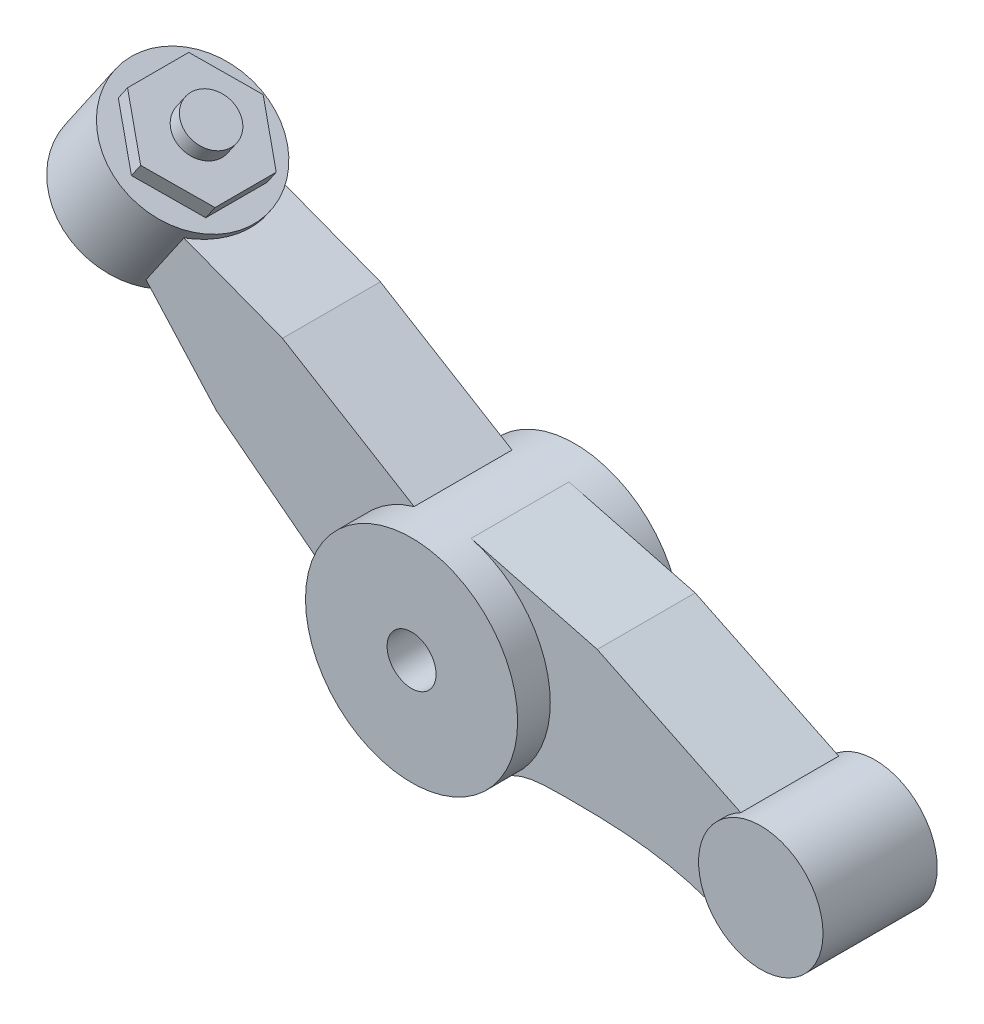
SolidWorks part; units mm, degrees
ref_plane "Front Plane" through (0, 0, 0) normal (0, 0, 1) x (1, 0, 0)
ref_plane "Top Plane" through (0, 0, 0) normal (0, 1, 0) x (1, 0, 0)
ref_plane "Right Plane" through (0, 0, 0) normal (1, 0, 0) x (0, 0, -1)
sketch "Sketch1" plane through (0, 0, 0) normal (0, 0, 1) x (1, 0, 0)
  line L0 (0, 0) -> (3.9859, 0) construction
  line L1 (0, 1.5974) -> (0, -1.3448) construction
  line L2 (0, 0) -> (-3.6604, 2.5129) construction
  line L3 (3.635, 0) -> (1.8753, 0.8528)
  line L4 (1.8753, 0.8528) -> (0.3293, 1.2576)
  line L5 (-3.468, 2.7932) -> (-3.8529, 2.2326)
  line L6 (-3.468, 2.7932) -> (-1.9822, 2.2255)
  line L7 (-1.9822, 2.2255) -> (-0.3688, 1.2466)
  line L8 (-2.7892, 1.0501) -> (-1.2958, -0.1038)
  line L9 (-3.8529, 2.2326) -> (-2.7892, 1.0501)
  circle A0 centre (0, 0) radius 0.3
  circle A1 centre (0, 0) radius 1.3
  circle A2 centre (3.98, -0.68) radius 0.7625
  spline S0 degree 3 poles (3.4329, -1.2112) (2.7827, -0.9275) (1.9247, -0.8957) (0.9499, -0.9165) (0.7651, -1.051) knots 0 0 0 0 0.749641 1 1 1 1
  dimension "D1" = 0.6
  dimension "D2" = 2.6
  dimension "D3" = 1.525
  dimension "D4" = 0.68
  dimension "D5" = 3.98
  dimension "D6" = 4.44
  dimension "D7" = 0.68
  dimension "D8" = 0.819
  dimension "D9" = 34.47
extrude "Boss-Extrude1" add sketch "Sketch1" along normal mid plane 2 contours A1 A0 region at (1, 0.7718, 0)
extrude "Boss-Extrude2" add sketch "Sketch1<3>" along normal mid plane 1.4 separate body contours A2 region at (3.98, -0.68, 0)
sketch "Sketch1<3>" plane through (0, 0, 0) normal (0, 0, 1) x (1, 0, 0) same geometry as "Sketch1"
extrude "Boss-Extrude3" add sketch "Sketch1<4>" along normal mid plane 1.2 contours S0 A2 L3 L4 A1 region at (2.1488, -0.1092, 0)
sketch "Sketch1<4>" plane through (0, 0, 0) normal (0, 0, 1) x (1, 0, 0) same geometry as "Sketch1"
extrude "Boss-Extrude4" add sketch "Sketch1<5>" along normal mid plane 1.2 contours A1 L7 L6 L5 L9 L8 region at (-2.1697, 1.4895, 0)
sketch "Sketch1<5>" plane through (0, 0, 0) normal (0, 0, 1) x (1, 0, 0) same geometry as "Sketch1"
sketch "Sketch2" plane through (0, 0, 0) normal (0, 0, 1) x (1, 0, 0)
  line L0 (-3.8529, 2.2326) -> (-3.4454, 2.8262)
  line L1 (-3.4454, 2.8262) -> (-3.771, 3.0498)
  line L2 (-3.771, 3.0498) -> (-4.8317, 1.5047)
  line L3 (-4.3623, 2.0144) -> (-3.8529, 2.2326)
  line L4 (-3.468, 2.7932) -> (-3.8529, 2.2326) construction
  arc A0 (-4.8317, 1.5047) -> (-4.3623, 2.0144) centre (-4.6336, 1.7932) ccw
  point P8 (-4.3746, 1.9323)
  point P9 (0, 0)
  dimension "D3" = 0.35
  dimension "D1" = 0.72
  dimension "D2" = 0.395
  dimension "D4" = 1
revolve "Revolve1" add sketch "Sketch2" angle 360 about L2
sketch "Sketch3" plane through (0, 0, 0) normal (0, 0, 1) x (1, 0, 0)
  line L0 (-3.6828, 3.1783) -> (-4.2917, 2.2913)
  line L1 (-4.2917, 2.2913) -> (-5.042, 2.8063)
  line L2 (-5.042, 2.8063) -> (-4.433, 3.6934)
  line L3 (-4.433, 3.6934) -> (-3.6828, 3.1783)
  line L5 (-4.5042, 2.6797) -> (-3.8529, 2.2326) construction
  line L6 (-3.4454, 2.8262) -> (-4.0967, 3.2733) construction
  point P3 (-4.1785, 2.4562)
  point P5 (-3.771, 3.0498)
  dimension "D1" = 1.076
  dimension "D2" = 0.91
revolve "Revolve2" add sketch "Sketch3" angle 360 about L0
sketch "Sketch4" plane through (0.3033, 0.4418, 0) normal (0.566, 0.8244, 0) x (0.8244, -0.566, 0)
  line L1 (-4.835, 0.7506) -> (-5.485, 0.3753)
  line L2 (-5.485, 0.3753) -> (-5.485, -0.3753)
  line L3 (-5.485, -0.3753) -> (-4.835, -0.7506)
  line L4 (-4.835, -0.7506) -> (-4.185, -0.3753)
  line L5 (-4.185, -0.3753) -> (-4.185, 0.3753)
  line L6 (-4.185, 0.3753) -> (-4.835, 0.7506)
  circle A0 centre (-4.835, 0) radius 0.65 construction
  dimension "D1" = 1.3
extrude "Boss-Extrude5" add sketch "Sketch4" along normal mid plane 0.4
sketch "Sketch5" plane through (0.4165, 0.6067, 0) normal (0.566, 0.8244, 0) x (0.8244, -0.566, 0)
  circle A0 centre (-4.835, 0) radius 0.3
  dimension "D1" = 0.6
extrude "Boss-Extrude6" add sketch "Sketch5" along normal mid plane 0.4
